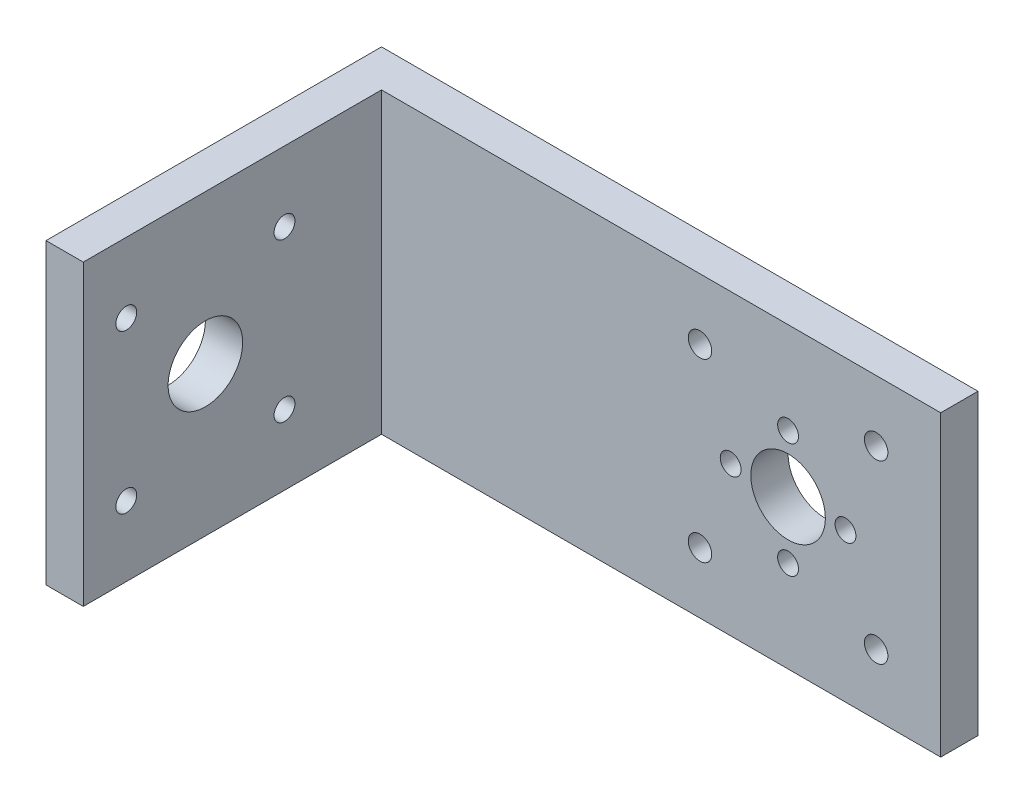
SolidWorks part; units mm, degrees
material "Copper"
ref_plane "Front Plane" through (0, 0, 0) normal (0, 0, 1) x (1, 0, 0)
ref_plane "Top Plane" through (0, 0, 0) normal (0, 1, 0) x (1, 0, 0)
ref_plane "Right Plane" through (0, 0, 0) normal (1, 0, 0) x (0, 0, -1)
sketch "Sketch1" plane through (0, 0, 0) normal (0, 0, 1) x (1, 0, 0)
  line L1 (0, 0) -> (-101.6, 0)
  line L2 (0, 0) -> (0, -50.8)
  line L3 (0, -50.8) -> (-101.6, -50.8)
  line L4 (-101.6, 0) -> (-101.6, -50.8)
  dimension "D1" = 50.8
  dimension "D2" = 101.6
extrude "Boss-Extrude1" add sketch "Sketch1" along normal blind 6.35
sketch "Sketch2" plane through (0, 0, 6.35) normal (0, 0, 1) x (1, 0, 0)
  line L0 (0, -25.4) -> (-101.6, -25.4) construction
  line L3 (0, -50.8) -> (0, 0) construction
  line L4 (-101.6, 0) -> (-101.6, -50.8) construction
  circle A0 centre (-11, -10.4) radius 2
  circle A1 centre (-41, -10.4) radius 2
  circle A2 centre (-41, -40.4) radius 2
  circle A3 centre (-11, -40.4) radius 2
  dimension "D1" = 15
  dimension "D7" = 4
  dimension "D8" = 4
  dimension "D9" = 4
  dimension "D10" = 4
  dimension "D2" = 15
  dimension "D3" = 15
  dimension "D4" = 15
  dimension "D5" = 30
  dimension "D6" = 30
  dimension "D11" = 11
  dimension "D12" = 11
extrude "Cut-Extrude1" cut sketch "Sketch2" against normal blind 6.35
sketch "Sketch3" plane through (0, 0, 6.35) normal (0, 0, 1) x (1, 0, 0)
  line L0 (0, -25.4) -> (-101.6, -25.4) construction
  line L1 (0, -50.8) -> (0, 0) construction
  line L2 (-101.6, 0) -> (-101.6, -50.8) construction
  circle A0 centre (-26, -15.621) radius 1.778
  dimension "D1" = 26
  dimension "D3" = 3.556
  dimension "D2" = 9.779
extrude "Cut-Extrude2" cut sketch "Sketch3" against normal blind 6.35
sketch "Sketch4" plane through (0, 0, 6.35) normal (0, 0, 1) x (1, 0, 0)
  line L0 (0, -25.4) -> (-101.6, -25.4) construction
  line L3 (0, -50.8) -> (0, 0) construction
  line L4 (-101.6, 0) -> (-101.6, -50.8) construction
  circle A0 centre (-26, -25.4) radius 6.35
  dimension "D1" = 12.7
  dimension "D2" = 26
extrude "Cut-Extrude3" cut sketch "Sketch4" against normal blind 6.35
pattern_circular "CirPattern1" count 4 over 360 about axis through (-26, -25.4, 6.35) along (0, 0, 1) of "Cut-Extrude2"
sketch "Sketch5" plane through (0, 0, 6.35) normal (0, 0, 1) x (1, 0, 0)
  line L0 (-101.6, -50.8) -> (0, -50.8) construction
  line L1 (-101.6, 0) -> (-95.25, 0)
  line L2 (-101.6, 0) -> (-101.6, -50.8)
  line L3 (-101.6, -50.8) -> (-95.25, -50.8)
  line L4 (-95.25, 0) -> (-95.25, -50.8)
  dimension "D1" = 6.35
extrude "Boss-Extrude2" add sketch "Sketch5" along normal blind 50.8
sketch "Sketch6" plane through (-95.25, 0, 0) normal (1, 0, 0) x (0, 0, -1)
  line L0 (-6.35, -50.8) -> (-6.35, 0) construction
  line L1 (-57.15, -50.8) -> (-6.35, -50.8) construction
  circle A0 centre (-36.35, -25.4) radius 6.35
  dimension "D1" = 30
  dimension "D2" = 12.7
  dimension "D3" = 25.4
extrude "Cut-Extrude4" cut sketch "Sketch6" against normal blind 6.35
sketch "Sketch7" plane through (-95.25, 0, 0) normal (1, 0, 0) x (0, 0, -1)
  circle A0 centre (-49.8247, -11.9253) radius 1.778
  circle A1 centre (-36.35, -25.4) radius 6.35 construction
  point P6 (-49.3608, -11.8802)
  dimension "D1" = 3.556
  dimension "D2" = 13.4747
  dimension "D3" = 13.4747
extrude "Cut-Extrude5" cut sketch "Sketch7" against normal blind 6.35
pattern_circular "CirPattern2" count 4 over 360 about axis through (-95.25, -25.4, 36.35) along (1, 0, 0) of "Cut-Extrude5"
